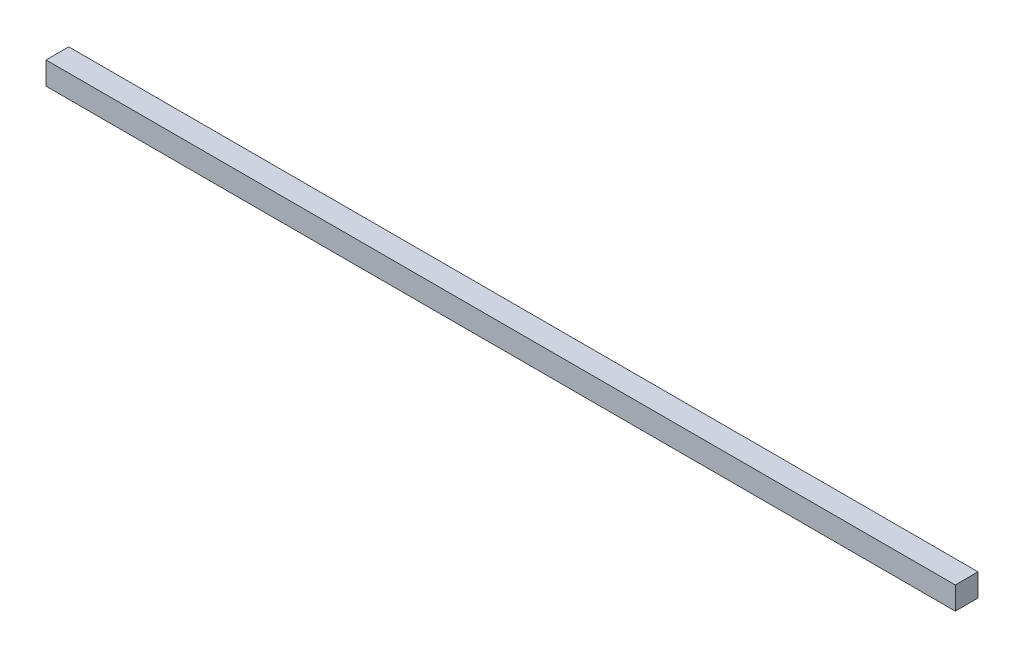
SolidWorks part; units mm, degrees
material "Plain Carbon Steel"
ref_plane "Front Plane" through (0, 0, 0) normal (0, 0, 1) x (1, 0, 0)
ref_plane "Top Plane" through (0, 0, 0) normal (0, 1, 0) x (1, 0, 0)
ref_plane "Right Plane" through (0, 0, 0) normal (1, 0, 0) x (0, 0, -1)
sketch "Sketch1" plane through (0, 0, 0) normal (0, 0, 1) x (1, 0, 0)
  line L0 (-200, -5) -> (200, -5)
  line L1 (200, -5) -> (200, 5)
  line L2 (200, 5) -> (-200, 5)
  line L3 (-200, 5) -> (-200, -5)
extrude "Boss-Extrude1" add sketch "Sketch1" along normal mid plane 10
